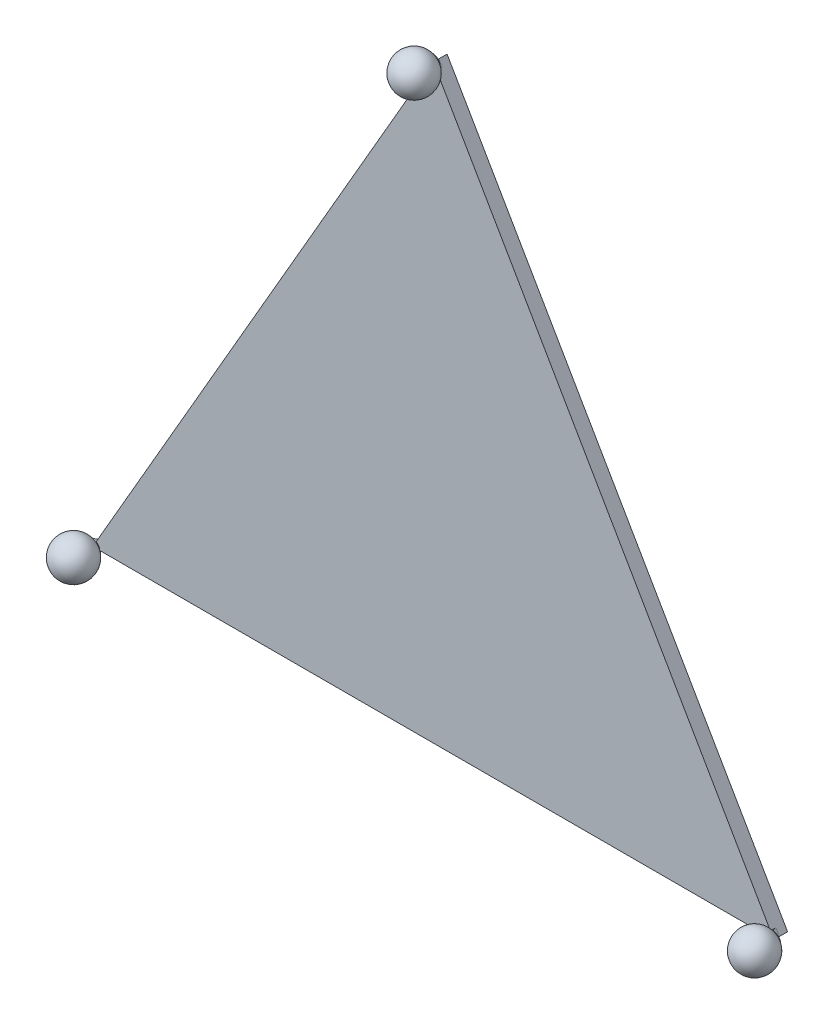
SolidWorks part; units mm, degrees
ref_plane "Front" through (0, 0, 0) normal (0, 0, 1) x (1, 0, 0)
ref_plane "Top" through (0, 0, 0) normal (0, 1, 0) x (1, 0, 0)
ref_plane "Right" through (0, 0, 0) normal (1, 0, 0) x (0, 0, -1)
sketch "Sketch1" plane through (0, 0, 0) normal (0, 0, 1) x (1, 0, 0)
  line L1 (0, 142.9029) -> (-123.7575, -71.4514)
  line L2 (-123.7575, -71.4514) -> (123.7575, -71.4514)
  line L3 (123.7575, -71.4514) -> (0, 142.9029)
  circle A0 centre (0, 0) radius 71.4514 construction
  dimension "D1" = 247.515
extrude "Boss-Extrude1" add sketch "Sketch1" along normal blind 5
sketch "Sketch2" plane through (0, 0, 5) normal (0, 0, 1) x (1, 0, 0)
  circle A0 centre (0, 142.9029) radius 2.5
  circle A1 centre (-123.7575, -71.4514) radius 2.5
  circle A2 centre (123.7575, -71.4514) radius 2.5
  dimension "D1" = 5
  dimension "D2" = 5
  dimension "D3" = 5
extrude "Boss-Extrude2" add sketch "Sketch2" along normal blind 7
sketch "Sketch3" plane through (0, 0, 12) normal (0, 0, 1) x (1, 0, 0)
  line L0 (0, 149.9029) -> (0, 135.9029)
  arc A0 (0, 135.9029) -> (0, 149.9029) centre (0, 142.9029) ccw
  dimension "D1" = 7
revolve "Revolve1" add sketch "Sketch3" angle 360 about L0
sketch "Sketch4" plane through (0, 0, 12) normal (0, 0, 1) x (1, 0, 0)
  line L0 (123.7575, -64.4514) -> (123.7575, -78.4514)
  arc A0 (123.7575, -78.4514) -> (123.7575, -64.4514) centre (123.7575, -71.4514) ccw
  dimension "D1" = 7
revolve "Revolve2" add sketch "Sketch4" angle 360 about L0
sketch "Sketch5" plane through (0, 0, 12) normal (0, 0, 1) x (1, 0, 0)
  line L0 (-123.7575, -64.4514) -> (-123.7575, -78.4514)
  arc A0 (-123.7575, -78.4514) -> (-123.7575, -64.4514) centre (-123.7575, -71.4514) ccw
  dimension "D1" = 7
revolve "Revolve3" add sketch "Sketch5" angle 360 about L0
fillet "Fillet1" radius 2 2 edges at (123.1325, -70.3689, 5) (122.5075, -71.4514, 5)
fillet "Fillet2" radius 2 4 edges at (0.625, 141.8203, 5) (-0.625, 141.8203, 5) (-123.1325, -70.3689, 5) (-122.5075, -71.4514, 5)
